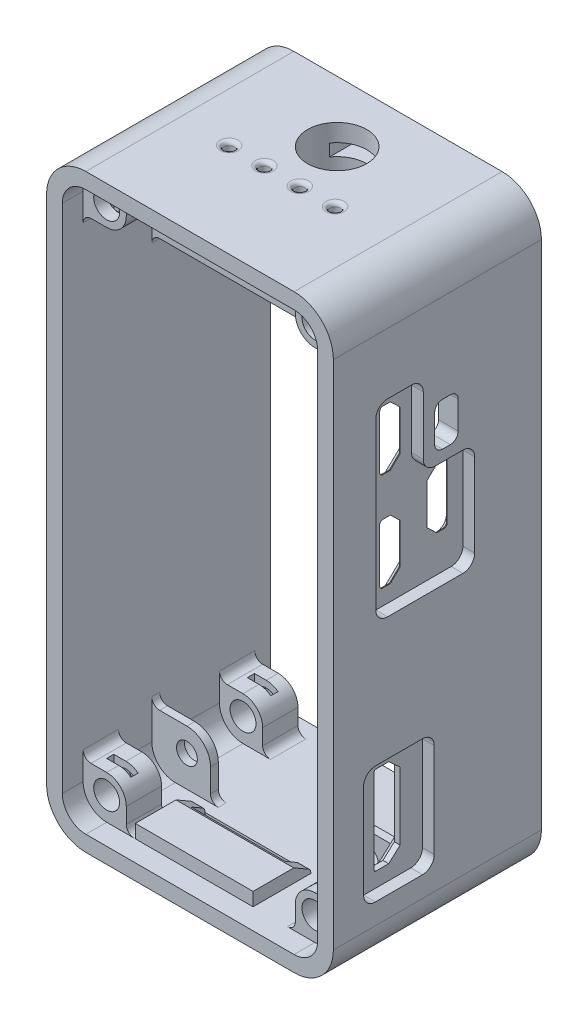
SolidWorks part; units mm, degrees
ref_plane "Front Plane" through (0, 0, 0) normal (0, 0, 1) x (1, 0, 0)
ref_plane "Top Plane" through (0, 0, 0) normal (0, 1, 0) x (1, 0, 0)
ref_plane "Right Plane" through (0, 0, 0) normal (1, 0, 0) x (0, 0, -1)
ref_plane "Plane1" through (15.42, 0, 0) normal (1, 0, 0) x (0, 0, -1)
ref_plane "Plane2" through (-16, 0, 0) normal (-1, 0, 0) x (0, 0, 1)
ref_plane "Plane3" through (0, 0, 12.35) normal (0, 0, -1) x (-1, 0, 0)
ref_plane "Plane4" through (0, 38.12, 0) normal (0, 1, 0) x (1, 0, 0)
ref_plane "Plane5" through (0, 0, -19.1) normal (0, 0, -1) x (-1, 0, 0)
ref_plane "Plane6" through (16.53, 0, 0) normal (1, 0, 0) x (0, 0, -1)
ref_plane "Plane7" through (0, -35, 0) normal (0, -1, 0) x (-1, 0, 0)
ref_axis "Axis1" through (16.53, -35, -39.8418) along (0, 0, 1)
ref_axis "Axis2" through (16.53, 38.12, 31.0702) along (0, 0, -1)
ref_axis "Axis3" through (16.53, 41.9436, 12.35) along (0, -1, 0)
ref_axis "Axis4" through (16.53, 40.8595, -19.1) along (0, -1, 0)
sketch "Sketch1" plane through (16.53, 0, 0) normal (1, 0, 0) x (0, 0, -1)
  line L0 (-31.0702, 38.12) -> (38.474, 38.12) construction
  line L1 (-12.35, 38.12) -> (19.1, 38.12)
  line L2 (-12.35, 38.12) -> (-12.35, -35)
  line L3 (-12.35, -35) -> (19.1, -35)
  line L4 (19.1, 38.12) -> (19.1, -35)
  line L6 (19.1, 40.8595) -> (19.1, -42.4423) construction
  line L7 (39.8418, -35) -> (-39.6201, -35) construction
  line L8 (-12.35, 41.9436) -> (-12.35, -39.5671) construction
extrude "Boss-Extrude1" add sketch "Sketch1" along normal blind 2
sketch "Sketch3" plane through (-16, 0, 0) normal (-1, 0, 0) x (0, 0, 1)
  line L4 (12.35, -35) -> (12.35, 38.12)
  line L5 (12.35, 38.12) -> (-19.1, 38.12)
  line L6 (-19.1, 38.12) -> (-19.1, -35)
  line L7 (-19.1, -35) -> (12.35, -35)
  line L8 (12.35, -35) -> (12.35, 38.12)
  line L9 (12.35, 38.12) -> (-19.1, 38.12)
  line L10 (-19.1, 38.12) -> (-19.1, -35)
  line L11 (-19.1, -35) -> (12.35, -35)
  dimension "D1" = 0
extrude "Boss-Extrude2" add sketch "Sketch3" along normal blind 2 separate body
sketch "Sketch4" plane through (0, 38.12, 0) normal (0, 1, 0) x (1, 0, 0)
  line L1 (-18, -12.35) -> (18.53, -12.35)
  line L2 (-18, -12.35) -> (-18, 19.1)
  line L3 (-18, 19.1) -> (18.53, 19.1)
  line L4 (18.53, -12.35) -> (18.53, 19.1)
extrude "Boss-Extrude3" add sketch "Sketch4" along normal blind 2
sketch "Sketch5" plane through (0, -35, 0) normal (0, -1, 0) x (1, 0, 0)
  line L1 (-18, 12.35) -> (18.53, 12.35)
  line L2 (-18, 12.35) -> (-18, -19.1)
  line L3 (-18, -19.1) -> (18.53, -19.1)
  line L4 (18.53, 12.35) -> (18.53, -19.1)
extrude "Boss-Extrude4" add sketch "Sketch5" against normal blind 2
fillet "Fillet1" radius 3 4 edges at (16.53, -33, -3.375) (16.53, 38.12, -3.375) (-16, 38.12, -3.375) (-16, -33, -3.375)
fillet "Fillet2" radius 5 4 edges at (-18, -35, -3.375) (18.53, -35, -3.375) (-18, 40.12, -3.375) (18.53, 40.12, -3.375)
sketch "Sketch6" plane through (18.53, 0, 0) normal (1, 0, 0) x (0, 0, -1)
  line L0 (-3.0523, 25.35) -> (-3.6, 25.35) construction
  line L3 (-2.3598, 18.0786) -> (-1.7075, 18.7048) construction
  line L4 (-3.6, 17.8) -> (-3.0523, 17.8) construction
  line L5 (-4, 24.95) -> (-4, 18.2) construction
  line L6 (-4, 24.95) -> (-4, 18.2)
  line L7 (-3.6, 17.8) -> (-2.65, 17.8)
  line L8 (-2.65, 17.8) -> (-1.4, 19)
  line L11 (-2.65, 25.35) -> (-3.6, 25.35)
  line L12 (-3.6, 5.3) -> (-3.0523, 5.3) construction
  line L13 (-2.3598, 5.5786) -> (-1.7075, 6.2048) construction
  line L14 (-1.4, 6.9262) -> (-1.4, 11.2238) construction
  line L15 (-1.7075, 11.9452) -> (-2.3598, 12.5714) construction
  line L16 (-3.0523, 12.85) -> (-3.6, 12.85) construction
  line L17 (-4, 12.45) -> (-4, 5.7) construction
  line L18 (-3.6, 5.3) -> (-2.65, 5.3)
  line L19 (-2.65, 5.3) -> (-1.4, 6.5)
  line L20 (-1.4, 6.5) -> (-1.4, 11.65)
  line L21 (-1.4, 11.65) -> (-2.65, 12.85)
  line L22 (-2.65, 12.85) -> (-3.6, 12.85)
  line L23 (-4, 12.45) -> (-4, 5.7)
  line L24 (4.2, 15.5) -> (3.6523, 15.5) construction
  line L25 (4.6, 8.35) -> (4.6, 15.1) construction
  line L26 (3.6523, 7.95) -> (4.2, 7.95) construction
  line L27 (2.3075, 8.8548) -> (2.9598, 8.2286) construction
  line L28 (2, 23.3) -> (2, 18.8)
  line L29 (2, 18.8) -> (4, 18.8)
  line L30 (4, 18.8) -> (4, 23.3)
  line L31 (4, 23.3) -> (2, 23.3)
  line L32 (2, 23.3) -> (2, 18.8) construction
  line L33 (2, 18.8) -> (4, 18.8) construction
  line L34 (4, 18.8) -> (4, 23.3) construction
  line L35 (4, 23.3) -> (2, 23.3) construction
  line L36 (2.5, 20.1) -> (3.5, 20.1)
  line L37 (3.5, 20.1) -> (3.5, 22)
  line L38 (3.5, 22) -> (2.5, 22)
  line L39 (2.5, 22) -> (2.5, 20.1)
  line L40 (2.5, 20.1) -> (3.5, 20.1) construction
  line L41 (3.5, 20.1) -> (3.5, 22) construction
  line L42 (3.5, 22) -> (2.5, 22) construction
  line L43 (2.5, 22) -> (2.5, 20.1) construction
  line L44 (2, 13.8738) -> (2, 9.5762) construction
  line L45 (2.9598, 15.2214) -> (2.3075, 14.5952) construction
  line L46 (4.2, 15.5) -> (3.25, 15.5)
  line L47 (4.6, 8.35) -> (4.6, 15.1)
  line L48 (3.25, 7.95) -> (4.2, 7.95)
  line L49 (2, 9.15) -> (3.25, 7.95)
  line L50 (2, 14.3) -> (2, 9.15)
  line L51 (3.25, 15.5) -> (2, 14.3)
  line L52 (-4.7, -14.45) -> (-4.7, -25.3) construction
  line L53 (-4.5, -25.5) -> (-2.9276, -25.5) construction
  line L54 (-2.7927, -25.4476) -> (-1.4651, -24.2345) construction
  line L55 (-2.9276, -14.25) -> (-4.5, -14.25) construction
  line L56 (-1.4651, -15.5155) -> (-2.7927, -14.3024) construction
  line L57 (-1.4, -24.0868) -> (-1.4, -15.6632) construction
  line L58 (-2.85, -14.25) -> (-4.5, -14.25)
  line L59 (-1.4, -15.575) -> (-2.85, -14.25)
  line L60 (-1.4, -24.175) -> (-1.4, -15.575)
  line L61 (-2.85, -25.5) -> (-1.4, -24.175)
  line L62 (-4.5, -25.5) -> (-2.85, -25.5)
  line L63 (-4.7, -14.45) -> (-4.7, -25.3)
  line L64 (-1.4, 24.15) -> (-2.65, 25.35)
  line L65 (-1.4, 19) -> (-1.4, 24.15)
  line L66 (1.5, 22.8) -> (1.5, 19.3)
  line L67 (2.5, 18.3) -> (3.5, 18.3)
  line L68 (4.5, 19.3) -> (4.5, 22.8)
  line L69 (3.5, 23.8) -> (2.5, 23.8)
  line L70 (1.5, 23.8) -> (1.5, 18.3) construction
  line L71 (1.5, 18.3) -> (4.5, 18.3) construction
  line L72 (4.5, 18.3) -> (4.5, 23.8) construction
  line L73 (4.5, 23.8) -> (1.5, 23.8) construction
  arc A0 (-4, 18.2) -> (-3.6, 17.8) centre (-3.6, 18.2) ccw construction
  arc A1 (-3.6, 25.35) -> (-4, 24.95) centre (-3.6, 24.95) ccw construction
  arc A6 (-4, 18.2) -> (-3.6, 17.8) centre (-3.6, 18.2) ccw
  arc A11 (-3.6, 25.35) -> (-4, 24.95) centre (-3.6, 24.95) ccw
  arc A12 (-4, 5.7) -> (-3.6, 5.3) centre (-3.6, 5.7) ccw construction
  arc A17 (-3.6, 12.85) -> (-4, 12.45) centre (-3.6, 12.45) ccw construction
  arc A18 (-4, 5.7) -> (-3.6, 5.3) centre (-3.6, 5.7) ccw
  arc A23 (-3.6, 12.85) -> (-4, 12.45) centre (-3.6, 12.45) ccw
  arc A25 (4.6, 15.1) -> (4.2, 15.5) centre (4.2, 15.1) ccw construction
  arc A26 (4.2, 7.95) -> (4.6, 8.35) centre (4.2, 8.35) ccw construction
  arc A31 (4.6, 15.1) -> (4.2, 15.5) centre (4.2, 15.1) ccw
  arc A32 (4.2, 7.95) -> (4.6, 8.35) centre (4.2, 8.35) ccw
  arc A37 (-4.7, -25.3) -> (-4.5, -25.5) centre (-4.5, -25.3) ccw construction
  arc A38 (-4.5, -14.25) -> (-4.7, -14.45) centre (-4.5, -14.45) ccw construction
  arc A42 (-4.5, -14.25) -> (-4.7, -14.45) centre (-4.5, -14.45) ccw
  arc A47 (-4.7, -25.3) -> (-4.5, -25.5) centre (-4.5, -25.3) ccw
  arc A48 (1.5, 19.3) -> (2.5, 18.3) centre (2.5, 19.3) ccw
  arc A49 (3.5, 18.3) -> (4.5, 19.3) centre (3.5, 19.3) ccw
  arc A50 (4.5, 22.8) -> (3.5, 23.8) centre (3.5, 22.8) ccw
  arc A51 (1.5, 22.8) -> (2.5, 23.8) centre (2.5, 22.8) cw
  dimension "D4" = 1
  dimension "D1" = 0
  dimension "D2" = 0
  dimension "D3" = 0.5
extrude "Cut-Extrude1" cut sketch "Sketch6" against normal blind 4
sketch "Sketch7" plane through (18.53, 0, 0) normal (1, 0, 0) x (0, 0, -1)
  line L0 (3.3166, 18.3) -> (3.3166, 15.5) construction
  line L1 (2.5, 18.3) -> (3.5, 18.3) construction
  line L2 (4.2, 15.5) -> (3.25, 15.5) construction
  line L3 (-1.4, 21.575) -> (1.5, 21.575) construction
  line L4 (-1.4, 19) -> (-1.4, 24.15) construction
  line L5 (1.5, 22.8) -> (1.5, 19.3) construction
  line L6 (0.05, 25.85) -> (0.05, 18.4)
  line L7 (1.55, 16.9) -> (5.1, 16.9)
  line L8 (-6, 25.85) -> (-6, 4.8)
  line L9 (-4, 24.95) -> (-4, 18.2) construction
  line L10 (-4.5, 27.35) -> (-1.45, 27.35)
  line L11 (-2.65, 25.35) -> (-3.6, 25.35) construction
  line L12 (-4.5, 3.3) -> (5.1, 3.3)
  line L13 (6.6, 4.8) -> (6.6, 15.4)
  line L14 (-3.6, 5.3) -> (-2.65, 5.3) construction
  line L15 (4.6, 8.35) -> (4.6, 15.1) construction
  line L16 (-4.7, -19.875) -> (-1.4, -19.875) construction
  line L17 (-6.05, -12.375) -> (-0.05, -12.375)
  line L18 (-7.55, -13.875) -> (-7.55, -25.875)
  line L19 (-6.05, -27.375) -> (-0.05, -27.375)
  line L20 (1.45, -13.875) -> (1.45, -25.875)
  line L21 (-4.7, -14.45) -> (-4.7, -25.3) construction
  line L22 (-1.4, -24.175) -> (-1.4, -15.575) construction
  line L23 (-3.05, -12.375) -> (-3.05, -27.375) construction
  arc A0 (-6, 4.8) -> (-4.5, 3.3) centre (-4.5, 4.8) ccw
  arc A1 (5.1, 3.3) -> (6.6, 4.8) centre (5.1, 4.8) ccw
  arc A2 (5.1, 16.9) -> (6.6, 15.4) centre (5.1, 15.4) cw
  arc A3 (1.55, 16.9) -> (0.05, 18.4) centre (1.55, 18.4) cw
  arc A4 (0.05, 25.85) -> (-1.45, 27.35) centre (-1.45, 25.85) ccw
  arc A5 (-6, 25.85) -> (-4.5, 27.35) centre (-4.5, 25.85) cw
  arc A6 (-0.05, -27.375) -> (1.45, -25.875) centre (-0.05, -25.875) ccw
  arc A7 (-0.05, -12.375) -> (1.45, -13.875) centre (-0.05, -13.875) cw
  arc A8 (-6.05, -12.375) -> (-7.55, -13.875) centre (-6.05, -13.875) ccw
  arc A9 (-7.55, -25.875) -> (-6.05, -27.375) centre (-6.05, -25.875) ccw
  point P14 (0.05, 21.575)
  point P17 (3.3166, 16.9)
  point P50 (-7.55, -19.875)
  point P53 (-3.05, -19.875)
  point P54 (-3.05, -19.875)
  dimension "D5" = 1.5
  dimension "D8" = 1.5
  dimension "D1" = 2
  dimension "D2" = 2
  dimension "D3" = 2
  dimension "D4" = 2
  dimension "D6" = 9
  dimension "D7" = 15
extrude "Cut-Extrude2" cut sketch "Sketch7" against normal blind 1.5
sketch "Sketch8" plane through (16.53, 0, 0) normal (-1, 0, 0) x (0, 0, 1)
  line L0 (7.2, 4.8) -> (7.2, 25.85)
  line L1 (4.5, 28.55) -> (1.45, 28.55)
  line L4 (-7.8, 15.4) -> (-7.8, 25.85)
  line L5 (-5.1, 28.55) -> (1.45, 28.55)
  line L6 (-5.1, 3.3) -> (4.5, 3.3)
  line L7 (-6.6, 15.4) -> (-6.6, 4.8)
  line L8 (-1.55, 16.9) -> (-5.1, 16.9)
  line L9 (-0.05, 25.85) -> (-0.05, 18.4)
  line L10 (4.5, 27.35) -> (1.45, 27.35)
  line L11 (6, 4.8) -> (6, 25.85)
  line L12 (-5.1, 3.3) -> (4.5, 3.3) construction
  line L13 (-6.6, 15.4) -> (-6.6, 4.8) construction
  line L14 (-1.55, 16.9) -> (-5.1, 16.9) construction
  line L15 (-0.05, 25.85) -> (-0.05, 18.4) construction
  line L16 (4.5, 27.35) -> (1.45, 27.35) construction
  line L17 (6, 4.8) -> (6, 25.85) construction
  line L18 (-2.5, 18.3) -> (-3.5, 18.3) construction
  line L19 (-1.5, 22.8) -> (-1.5, 19.3) construction
  line L24 (-7.8, 15.4) -> (-7.8, 4.8)
  line L25 (-5.1, 2.1) -> (4.5, 2.1)
  line L42 (2.65, 25.35) -> (1.4, 24.15) construction
  line L43 (3.6, 25.35) -> (2.65, 25.35) construction
  line L44 (4, 18.2) -> (4, 24.95) construction
  line L45 (2.65, 17.8) -> (3.6, 17.8) construction
  line L46 (1.4, 19) -> (2.65, 17.8) construction
  line L47 (1.4, 24.15) -> (1.4, 19) construction
  line L48 (2.65, 25.35) -> (1.4, 24.15)
  line L49 (3.6, 25.35) -> (2.65, 25.35)
  line L50 (4, 18.2) -> (4, 24.95)
  line L51 (2.65, 17.8) -> (3.6, 17.8)
  line L52 (1.4, 19) -> (2.65, 17.8)
  line L53 (1.4, 24.15) -> (1.4, 19)
  line L54 (1.4, 11.65) -> (1.4, 6.5) construction
  line L55 (1.4, 6.5) -> (2.65, 5.3) construction
  line L56 (2.65, 5.3) -> (3.6, 5.3) construction
  line L57 (4, 5.7) -> (4, 12.45) construction
  line L58 (2.65, 12.85) -> (1.4, 11.65) construction
  line L59 (3.6, 12.85) -> (2.65, 12.85) construction
  line L60 (1.4, 11.65) -> (1.4, 6.5)
  line L61 (1.4, 6.5) -> (2.65, 5.3)
  line L62 (2.65, 5.3) -> (3.6, 5.3)
  line L63 (4, 5.7) -> (4, 12.45)
  line L64 (2.65, 12.85) -> (1.4, 11.65)
  line L65 (3.6, 12.85) -> (2.65, 12.85)
  line L66 (-4.2, 7.95) -> (-3.25, 7.95) construction
  line L67 (-4.6, 15.1) -> (-4.6, 8.35) construction
  line L68 (-3.25, 15.5) -> (-4.2, 15.5) construction
  line L69 (-2, 14.3) -> (-3.25, 15.5) construction
  line L70 (-2, 9.15) -> (-2, 14.3) construction
  line L71 (-3.25, 7.95) -> (-2, 9.15) construction
  line L72 (-4.2, 7.95) -> (-3.25, 7.95)
  line L73 (-4.6, 15.1) -> (-4.6, 8.35)
  line L74 (-3.25, 15.5) -> (-4.2, 15.5)
  line L75 (-2, 14.3) -> (-3.25, 15.5)
  line L76 (-2, 9.15) -> (-2, 14.3)
  line L77 (-3.25, 7.95) -> (-2, 9.15)
  line L78 (-3.5, 23.8) -> (-2.5, 23.8) construction
  line L79 (-4.5, 19.3) -> (-4.5, 22.8) construction
  line L80 (-2.5, 18.3) -> (-3.5, 18.3)
  line L81 (-1.5, 22.8) -> (-1.5, 19.3)
  line L82 (-3.5, 23.8) -> (-2.5, 23.8)
  line L83 (-4.5, 19.3) -> (-4.5, 22.8)
  line L88 (-1.25, 25.85) -> (-1.25, 18.4) construction
  line L89 (-1.55, 18.1) -> (-5.1, 18.1) construction
  arc A0 (4.5, 2.1) -> (7.2, 4.8) centre (4.5, 4.8) ccw
  arc A1 (7.2, 25.85) -> (4.5, 28.55) centre (4.5, 25.85) ccw
  arc A4 (-7.8, 25.85) -> (-5.1, 28.55) centre (-5.1, 25.85) cw
  arc A5 (-4.5, 19.3) -> (-3.5, 18.3) centre (-3.5, 19.3) ccw construction
  arc A6 (4.5, 3.3) -> (6, 4.8) centre (4.5, 4.8) ccw
  arc A7 (-6.6, 4.8) -> (-5.1, 3.3) centre (-5.1, 4.8) ccw
  arc A8 (-5.1, 16.9) -> (-6.6, 15.4) centre (-5.1, 15.4) ccw
  arc A9 (-1.55, 16.9) -> (-0.05, 18.4) centre (-1.55, 18.4) ccw
  arc A10 (1.45, 27.35) -> (-0.05, 25.85) centre (1.45, 25.85) ccw
  arc A11 (6, 25.85) -> (4.5, 27.35) centre (4.5, 25.85) ccw
  arc A12 (4.5, 3.3) -> (6, 4.8) centre (4.5, 4.8) ccw construction
  arc A13 (-6.6, 4.8) -> (-5.1, 3.3) centre (-5.1, 4.8) ccw construction
  arc A14 (-5.1, 16.9) -> (-6.6, 15.4) centre (-5.1, 15.4) ccw construction
  arc A15 (-1.55, 16.9) -> (-0.05, 18.4) centre (-1.55, 18.4) ccw construction
  arc A16 (1.45, 27.35) -> (-0.05, 25.85) centre (1.45, 25.85) ccw construction
  arc A17 (6, 25.85) -> (4.5, 27.35) centre (4.5, 25.85) ccw construction
  arc A18 (-2.5, 18.3) -> (-1.5, 19.3) centre (-2.5, 19.3) ccw construction
  arc A19 (-1.5, 22.8) -> (-2.5, 23.8) centre (-2.5, 22.8) ccw construction
  arc A25 (-7.8, 4.8) -> (-5.1, 2.1) centre (-5.1, 4.8) ccw
  arc A34 (4, 24.95) -> (3.6, 25.35) centre (3.6, 24.95) ccw construction
  arc A35 (3.6, 17.8) -> (4, 18.2) centre (3.6, 18.2) ccw construction
  arc A36 (4, 24.95) -> (3.6, 25.35) centre (3.6, 24.95) ccw
  arc A37 (3.6, 17.8) -> (4, 18.2) centre (3.6, 18.2) ccw
  arc A38 (3.6, 5.3) -> (4, 5.7) centre (3.6, 5.7) ccw construction
  arc A39 (4, 12.45) -> (3.6, 12.85) centre (3.6, 12.45) ccw construction
  arc A40 (3.6, 5.3) -> (4, 5.7) centre (3.6, 5.7) ccw
  arc A41 (4, 12.45) -> (3.6, 12.85) centre (3.6, 12.45) ccw
  arc A42 (-4.6, 8.35) -> (-4.2, 7.95) centre (-4.2, 8.35) ccw construction
  arc A43 (-4.2, 15.5) -> (-4.6, 15.1) centre (-4.2, 15.1) ccw construction
  arc A44 (-4.6, 8.35) -> (-4.2, 7.95) centre (-4.2, 8.35) ccw
  arc A45 (-4.2, 15.5) -> (-4.6, 15.1) centre (-4.2, 15.1) ccw
  arc A46 (-3.5, 23.8) -> (-4.5, 22.8) centre (-3.5, 22.8) ccw construction
  arc A47 (-4.5, 19.3) -> (-3.5, 18.3) centre (-3.5, 19.3) ccw
  arc A48 (-2.5, 18.3) -> (-1.5, 19.3) centre (-2.5, 19.3) ccw
  arc A49 (-1.5, 22.8) -> (-2.5, 23.8) centre (-2.5, 22.8) ccw
  arc A50 (-3.5, 23.8) -> (-4.5, 22.8) centre (-3.5, 22.8) ccw
  arc A56 (1.45, 28.55) -> (-1.25, 25.85) centre (1.45, 25.85) ccw construction
  arc A57 (-1.55, 18.1) -> (-1.25, 18.4) centre (-1.55, 18.4) ccw construction
  arc A58 (-5.1, 18.1) -> (-7.8, 15.4) centre (-5.1, 15.4) ccw construction
  dimension "D2" = 2.7
  dimension "D1" = 0
  dimension "D3" = 1.2
extrude "Boss-Extrude5" add sketch "Sketch8" along normal blind 0.5
sketch "Sketch9" plane through (16.53, 0, 0) normal (-1, 0, 0) x (0, 0, 1)
  line L0 (0.05, -28.575) -> (6.05, -28.575)
  line L1 (8.75, -25.875) -> (8.75, -13.875)
  line L2 (6.05, -11.175) -> (0.05, -11.175)
  line L3 (-2.65, -13.875) -> (-2.65, -25.875)
  line L4 (-1.45, -13.875) -> (-1.45, -25.875)
  line L5 (6.05, -12.375) -> (0.05, -12.375)
  line L6 (7.55, -25.875) -> (7.55, -13.875)
  line L7 (0.05, -27.375) -> (6.05, -27.375)
  line L8 (-1.45, -13.875) -> (-1.45, -25.875) construction
  line L9 (6.05, -12.375) -> (0.05, -12.375) construction
  line L10 (7.55, -25.875) -> (7.55, -13.875) construction
  line L11 (0.05, -27.375) -> (6.05, -27.375) construction
  line L12 (1.4, -24.175) -> (2.85, -25.5) construction
  line L13 (2.85, -25.5) -> (4.5, -25.5) construction
  line L14 (1.4, -15.575) -> (1.4, -24.175) construction
  line L15 (2.85, -14.25) -> (1.4, -15.575) construction
  line L16 (4.5, -14.25) -> (2.85, -14.25) construction
  line L17 (4.7, -25.3) -> (4.7, -14.45) construction
  line L18 (1.4, -24.175) -> (2.85, -25.5)
  line L19 (2.85, -25.5) -> (4.5, -25.5)
  line L20 (1.4, -15.575) -> (1.4, -24.175)
  line L21 (2.85, -14.25) -> (1.4, -15.575)
  line L22 (4.5, -14.25) -> (2.85, -14.25)
  line L23 (4.7, -25.3) -> (4.7, -14.45)
  line L24 (8.75, -25.875) -> (8.75, -28.575)
  line L25 (8.75, -28.575) -> (6.05, -28.575)
  arc A0 (-2.65, -25.875) -> (0.05, -28.575) centre (0.05, -25.875) ccw
  arc A1 (6.05, -28.575) -> (8.75, -25.875) centre (6.05, -25.875) ccw construction
  arc A2 (8.75, -13.875) -> (6.05, -11.175) centre (6.05, -13.875) ccw
  arc A3 (0.05, -11.175) -> (-2.65, -13.875) centre (0.05, -13.875) ccw
  arc A4 (-1.45, -25.875) -> (0.05, -27.375) centre (0.05, -25.875) ccw
  arc A5 (0.05, -12.375) -> (-1.45, -13.875) centre (0.05, -13.875) ccw
  arc A6 (7.55, -13.875) -> (6.05, -12.375) centre (6.05, -13.875) ccw
  arc A7 (6.05, -27.375) -> (7.55, -25.875) centre (6.05, -25.875) ccw
  arc A8 (-1.45, -25.875) -> (0.05, -27.375) centre (0.05, -25.875) ccw construction
  arc A9 (0.05, -12.375) -> (-1.45, -13.875) centre (0.05, -13.875) ccw construction
  arc A10 (7.55, -13.875) -> (6.05, -12.375) centre (6.05, -13.875) ccw construction
  arc A11 (6.05, -27.375) -> (7.55, -25.875) centre (6.05, -25.875) ccw construction
  arc A12 (4.5, -25.5) -> (4.7, -25.3) centre (4.5, -25.3) ccw construction
  arc A13 (4.7, -14.45) -> (4.5, -14.25) centre (4.5, -14.45) ccw construction
  arc A14 (4.5, -25.5) -> (4.7, -25.3) centre (4.5, -25.3) ccw
  arc A15 (4.7, -14.45) -> (4.5, -14.25) centre (4.5, -14.45) ccw
  dimension "D1" = 0
  dimension "D2" = 1.2
extrude "Boss-Extrude6" add sketch "Sketch9" along normal up to surface (1.13 mm away)
chamfer "Chamfer1" distance 0.9 angle 45 32 edges at (16.03, 12.25, 2.025) (16.03, 5.9, 2.025) (16.03, 9.075, 1.4) (16.03, 24.75, 2.025) (16.03, 18.4, 2.025) (16.03, 21.575, 1.4) (16.03, 8.55, -2.625) (16.03, 14.9, -2.625) (16.03, 11.725, -2) (16.03, 15.5, -3.725) (16.03, 7.95, -3.725) (16.03, 15.3828, -4.4828) (16.03, 8.0672, -4.4828) (16.03, 11.725, -4.6) (16.03, 5.3, 3.125) (16.03, 12.85, 3.125) (16.03, 5.4172, 3.8828) (16.03, 12.7328, 3.8828) (16.03, 9.075, 4) (16.03, 17.8, 3.125) (16.03, 25.35, 3.125) (16.03, 17.9172, 3.8828) (16.03, 25.2328, 3.8828) (16.03, 21.575, 4) (15.4, -14.9125, 2.125) (15.4, -19.875, 1.4) (15.4, -24.8375, 2.125) (15.4, -25.5, 3.675) (15.4, -14.25, 3.675) (15.4, -25.4414, 4.6414) (15.4, -14.3086, 4.6414) (15.4, -19.875, 4.7)
sketch "Sketch10" plane through (0, -35, 0) normal (0, -1, 0) x (1, 0, 0)
  line L0 (4.15, 2.75) -> (4.15, 1.4) construction
  line L1 (1.65, 2.85) -> (4.05, 2.85) construction
  line L2 (4.15, 1.4) -> (1.65, 1.4) construction
  line L3 (1.65, 1.4) -> (1.65, 2.85) construction
  line L4 (-7.85, 1.4) -> (-7.85, 2.75) construction
  line L5 (-7.75, 2.85) -> (-6.75, 2.85) construction
  line L6 (-6.75, 2.85) -> (-6.75, 1.4) construction
  line L7 (-6.75, 1.4) -> (-7.85, 1.4) construction
  line L8 (1.65, 2.85) -> (4.05, 2.85) construction
  line L9 (4.15, 2.75) -> (4.15, 1.4) construction
  line L10 (4.15, 1.4) -> (1.65, 1.4) construction
  line L11 (1.65, 1.4) -> (1.65, 2.85) construction
  line L12 (-7.85, 1.4) -> (-7.85, 2.75) construction
  line L13 (-7.75, 2.85) -> (-6.75, 2.85) construction
  line L14 (-6.75, 2.85) -> (-6.75, 1.4) construction
  line L15 (-6.75, 1.4) -> (-7.85, 1.4) construction
  line L17 (4.15, 1.4) -> (-7.85, 1.4)
  line L18 (4.15, 1.4) -> (4.15, 3.1408)
  line L19 (4.15, 3.1408) -> (-7.85, 3.1408)
  line L20 (-7.85, 1.4) -> (-7.85, 3.1408)
  arc A0 (4.15, 2.75) -> (4.05, 2.85) centre (4.05, 2.75) ccw construction
  arc A1 (-7.75, 2.85) -> (-7.85, 2.75) centre (-7.75, 2.75) ccw construction
  arc A2 (4.15, 2.75) -> (4.05, 2.85) centre (4.05, 2.75) ccw construction
  arc A3 (-7.75, 2.85) -> (-7.85, 2.75) centre (-7.75, 2.75) ccw construction
extrude "Cut-Extrude3" cut sketch "Sketch10" against normal blind 3
sketch "Sketch11" plane through (0, -33, 0) normal (0, 1, 0) x (1, 0, 0)
  line L0 (-7.85, -1.4) -> (4.15, -1.4) construction
  line L1 (5.65, -7.1408) -> (-9.35, -7.1408)
  line L2 (5.65, -7.1408) -> (5.65, -1.4)
  line L3 (5.65, -1.4) -> (4.15, -1.4)
  line L4 (-9.35, -7.1408) -> (-9.35, -1.4)
  line L5 (4.15, -1.4) -> (4.15, -3.1408) construction
  line L6 (-7.85, -3.1408) -> (-7.85, -1.4) construction
  line L7 (4.15, -3.1408) -> (-7.85, -3.1408) construction
  line L8 (4.15, -1.4) -> (4.15, -3.1408) construction
  line L9 (4.15, -3.1408) -> (-7.85, -3.1408) construction
  line L10 (-7.85, -3.1408) -> (-7.85, -1.4) construction
  line L11 (4.15, -1.4) -> (4.15, -3.1408)
  line L12 (4.15, -3.1408) -> (-7.85, -3.1408)
  line L13 (-7.85, -3.1408) -> (-7.85, -1.4)
  line L14 (-7.85, -1.4) -> (-9.35, -1.4)
  dimension "D1" = 1.5
  dimension "D2" = 1.5
  dimension "D3" = 4
extrude "Boss-Extrude7" add sketch "Sketch11" along normal blind 1.7
sketch "Sketch12" plane through (0, 0, 3.1408) normal (0, 0, -1) x (-1, 0, 0)
  line L0 (-4.15, -35) -> (7.85, -35) construction
  line L1 (-4.15, -35) -> (7.85, -35) construction
  line L2 (9.4089, -39.5975) -> (-5.7089, -39.5975)
  arc A0 (9.4089, -39.5975) -> (-5.7089, -39.5975) centre (1.85, -39.5975) ccw
revolve "Cut-Revolve1" cut sketch "Sketch12" angle 90 about L2
fillet "Fillet4" radius 0.5 1 edges at (-1.85, -32.0386, 3.1408)
sketch "Sketch14" plane through (0, 40.12, 0) normal (0, 1, 0) x (1, 0, 0)
  line L0 (7.4, 1) -> (6.1, 1) construction
  line L1 (6.1, 1) -> (6.1, 0.8) construction
  line L2 (6.1, 0.8) -> (7.4, 0.8) construction
  line L3 (7.4, 0.8) -> (7.4, 1) construction
  line L4 (7.4, 0.8) -> (6.1, 0.8) construction
  line L5 (6.1, 0.8) -> (6.1, 0.2) construction
  line L6 (6.1, 0.2) -> (7.4, 0.2) construction
  line L7 (7.4, 0.2) -> (7.4, 0.8) construction
  line L8 (7.4, 1) -> (6.1, 1) construction
  line L9 (6.1, 1) -> (6.1, 0.8) construction
  line L10 (6.1, 0.8) -> (7.4, 0.8) construction
  line L11 (7.4, 0.8) -> (7.4, 1) construction
  line L12 (7.4, 0.8) -> (6.1, 0.8) construction
  line L13 (6.1, 0.8) -> (6.1, 0.2) construction
  line L14 (6.1, 0.2) -> (7.4, 0.2) construction
  line L15 (7.4, 0.2) -> (7.4, 0.8) construction
  line L16 (2.9, 1) -> (1.6, 1) construction
  line L17 (1.6, 1) -> (1.6, 0.8) construction
  line L18 (1.6, 0.8) -> (2.9, 0.8) construction
  line L19 (2.9, 0.8) -> (2.9, 1) construction
  line L20 (2.9, 0.8) -> (1.6, 0.8) construction
  line L21 (1.6, 0.8) -> (1.6, 0.2) construction
  line L22 (1.6, 0.2) -> (2.9, 0.2) construction
  line L23 (2.9, 0.2) -> (2.9, 0.8) construction
  line L24 (2.9, 1) -> (1.6, 1) construction
  line L25 (1.6, 1) -> (1.6, 0.8) construction
  line L26 (1.6, 0.8) -> (2.9, 0.8) construction
  line L27 (2.9, 0.8) -> (2.9, 1) construction
  line L28 (2.9, 0.8) -> (1.6, 0.8) construction
  line L29 (1.6, 0.8) -> (1.6, 0.2) construction
  line L30 (1.6, 0.2) -> (2.9, 0.2) construction
  line L31 (2.9, 0.2) -> (2.9, 0.8) construction
  line L32 (-1.6, 1) -> (-2.9, 1) construction
  line L33 (-2.9, 1) -> (-2.9, 0.8) construction
  line L34 (-2.9, 0.8) -> (-1.6, 0.8) construction
  line L35 (-1.6, 0.8) -> (-1.6, 1) construction
  line L36 (-1.6, 0.8) -> (-2.9, 0.8) construction
  line L37 (-2.9, 0.8) -> (-2.9, 0.2) construction
  line L38 (-2.9, 0.2) -> (-1.6, 0.2) construction
  line L39 (-1.6, 0.2) -> (-1.6, 0.8) construction
  line L40 (-1.6, 1) -> (-2.9, 1) construction
  line L41 (-2.9, 1) -> (-2.9, 0.8) construction
  line L42 (-2.9, 0.8) -> (-1.6, 0.8) construction
  line L43 (-1.6, 0.8) -> (-1.6, 1) construction
  line L44 (-1.6, 0.8) -> (-2.9, 0.8) construction
  line L45 (-2.9, 0.8) -> (-2.9, 0.2) construction
  line L46 (-2.9, 0.2) -> (-1.6, 0.2) construction
  line L47 (-1.6, 0.2) -> (-1.6, 0.8) construction
  line L48 (-6.1, 1) -> (-7.4, 1) construction
  line L49 (-7.4, 1) -> (-7.4, 0.8) construction
  line L50 (-7.4, 0.8) -> (-6.1, 0.8) construction
  line L51 (-6.1, 0.8) -> (-6.1, 1) construction
  line L52 (-6.1, 0.8) -> (-7.4, 0.8) construction
  line L53 (-7.4, 0.8) -> (-7.4, 0.2) construction
  line L54 (-7.4, 0.2) -> (-6.1, 0.2) construction
  line L55 (-6.1, 0.2) -> (-6.1, 0.8) construction
  line L56 (-6.1, 1) -> (-7.4, 1) construction
  line L57 (-7.4, 1) -> (-7.4, 0.8) construction
  line L58 (-7.4, 0.8) -> (-6.1, 0.8) construction
  line L59 (-6.1, 0.8) -> (-6.1, 1) construction
  line L60 (-6.1, 0.8) -> (-7.4, 0.8) construction
  line L61 (-7.4, 0.8) -> (-7.4, 0.2) construction
  line L62 (-7.4, 0.2) -> (-6.1, 0.2) construction
  line L63 (-6.1, 0.2) -> (-6.1, 0.8) construction
  line L64 (6.75, 1) -> (6.75, 0.2) construction
  line L65 (2.25, 1) -> (2.25, 0.2) construction
  line L66 (-2.25, 1) -> (-2.25, 0.2) construction
  line L67 (-6.75, 1) -> (-6.75, 0.2) construction
  circle A0 centre (6.75, 0.6) radius 0.65
  circle A1 centre (2.25, 0.6) radius 0.65
  circle A2 centre (-2.25, 0.6) radius 0.65
  circle A3 centre (-6.75, 0.6) radius 0.65
  point P48 (6.75, -0.05)
extrude "Cut-Extrude4" cut sketch "Sketch14" against normal up to next
fillet "Fillet5" radius 0.5 4 edges at (-6.75, 40.12, 0.05) (-2.25, 40.12, 0.05) (2.25, 40.12, 0.05) (6.75, 40.12, 0.05)
sketch "Sketch15" plane through (0, 0, 0) normal (0, 0, -1) x (-1, 0, 0)
  line L0 (-13.53, 38.12) -> (13, 38.12) construction
  line L1 (16, 35.12) -> (16, -30) construction
  line L2 (-16.53, -30) -> (-16.53, 35.12) construction
  line L3 (13, -33) -> (-13.53, -33) construction
  line L4 (15, -28.75) -> (15, 28.75)
  line L5 (11.25, 32.5) -> (-11.25, 32.5)
  line L6 (-15, 28.75) -> (-15, -28.75)
  line L7 (-11.25, -32.5) -> (11.25, -32.5)
  line L8 (15, -28.75) -> (15, 28.75) construction
  line L9 (11.25, 32.5) -> (-11.25, 32.5) construction
  line L10 (-15, 28.75) -> (-15, -28.75) construction
  line L11 (-11.25, -32.5) -> (11.25, -32.5) construction
  line L12 (13, -33) -> (-13.53, -33)
  line L13 (-16.53, -30) -> (-16.53, 35.12)
  line L14 (16, 35.12) -> (16, -30)
  line L15 (-13.53, 38.12) -> (13, 38.12)
  circle A0 centre (11.525, 29.025) radius 1.325 construction
  circle A1 centre (11.525, 29.025) radius 1.325
  circle A2 centre (-11.525, 29.025) radius 1.325 construction
  circle A3 centre (-11.525, 29.025) radius 1.325
  arc A4 (11.25, -32.5) -> (15, -28.75) centre (11.25, -28.75) ccw
  arc A5 (15, 28.75) -> (11.25, 32.5) centre (11.25, 28.75) ccw
  arc A6 (-11.25, 32.5) -> (-15, 28.75) centre (-11.25, 28.75) ccw
  arc A7 (-15, -28.75) -> (-11.25, -32.5) centre (-11.25, -28.75) ccw
  arc A8 (11.25, -32.5) -> (15, -28.75) centre (11.25, -28.75) ccw construction
  arc A9 (15, 28.75) -> (11.25, 32.5) centre (11.25, 28.75) ccw construction
  arc A10 (-11.25, 32.5) -> (-15, 28.75) centre (-11.25, 28.75) ccw construction
  arc A11 (-15, -28.75) -> (-11.25, -32.5) centre (-11.25, -28.75) ccw construction
  circle A12 centre (-11.525, -29.025) radius 1.325 construction
  circle A13 centre (-11.525, -29.025) radius 1.325
  circle A14 centre (11.525, -29.025) radius 1.325 construction
  circle A15 centre (11.525, -29.025) radius 1.325
  arc A16 (-13.53, 38.12) -> (-16.53, 35.12) centre (-13.53, 35.12) ccw construction
  arc A17 (16, 35.12) -> (13, 38.12) centre (13, 35.12) ccw construction
  arc A18 (13, -33) -> (16, -30) centre (13, -30) ccw construction
  arc A19 (-16.53, -30) -> (-13.53, -33) centre (-13.53, -30) ccw construction
  arc A20 (13, -33) -> (16, -30) centre (13, -30) ccw
  arc A21 (-16.53, -30) -> (-13.53, -33) centre (-13.53, -30) ccw
  arc A22 (-13.53, 38.12) -> (-16.53, 35.12) centre (-13.53, 35.12) ccw
  arc A23 (16, 35.12) -> (13, 38.12) centre (13, 35.12) ccw
  dimension "D1" = 0
sketch "Sketch16" plane through (0, 0, 0) normal (0, 0, -1) x (-1, 0, 0)
  line L0 (-13.53, 38.12) -> (13, 38.12) construction
  line L1 (-16.53, -30) -> (-16.53, 35.12) construction
  line L2 (13, -33) -> (-13.53, -33) construction
  line L3 (16, 35.12) -> (16, -30) construction
  line L4 (-13.53, 38.12) -> (13, 38.12)
  line L5 (-16.53, -30) -> (-16.53, -26.025)
  line L6 (13, -33) -> (8.525, -33)
  line L7 (16, 35.12) -> (16, 26.025)
  line L8 (-8.525, -29.025) -> (-8.525, -33)
  line L9 (-11.525, -26.025) -> (-16.53, -26.025)
  line L10 (11.525, -26.025) -> (16, -26.025)
  line L11 (8.525, -29.025) -> (8.525, -33)
  line L12 (-16.53, 26.025) -> (16, 26.025)
  line L13 (-16.53, 26.025) -> (-16.53, 35.12)
  line L14 (16, -26.025) -> (16, -30)
  line L15 (-8.525, -33) -> (-13.53, -33)
  arc A0 (16, 35.12) -> (13, 38.12) centre (13, 35.12) ccw construction
  arc A1 (-13.53, 38.12) -> (-16.53, 35.12) centre (-13.53, 35.12) ccw construction
  arc A2 (-16.53, -30) -> (-13.53, -33) centre (-13.53, -30) ccw construction
  arc A3 (13, -33) -> (16, -30) centre (13, -30) ccw construction
  arc A4 (16, 35.12) -> (13, 38.12) centre (13, 35.12) ccw
  arc A5 (-13.53, 38.12) -> (-16.53, 35.12) centre (-13.53, 35.12) ccw
  arc A6 (-16.53, -30) -> (-13.53, -33) centre (-13.53, -30) ccw
  arc A7 (13, -33) -> (16, -30) centre (13, -30) ccw
  circle A8 centre (-11.525, 29.025) radius 1.325 construction
  circle A9 centre (-11.525, 29.025) radius 1.325
  circle A10 centre (11.525, 29.025) radius 1.325 construction
  circle A11 centre (11.525, 29.025) radius 1.325
  circle A12 centre (11.525, -29.025) radius 1.325 construction
  circle A13 centre (11.525, -29.025) radius 1.325
  circle A14 centre (-11.525, -29.025) radius 1.325 construction
  circle A15 centre (-11.525, -29.025) radius 1.325
  circle A16 centre (-11.525, -29.025) radius 3 construction
  circle A17 centre (11.525, -29.025) radius 3 construction
  circle A18 centre (-11.525, 29.025) radius 3 construction
  circle A19 centre (11.525, 29.025) radius 3 construction
  arc A20 (-8.525, -29.025) -> (-11.525, -26.025) centre (-11.525, -29.025) ccw
  arc A21 (11.525, -26.025) -> (8.525, -29.025) centre (11.525, -29.025) ccw
  circle A22 centre (-11.525, 29.025) radius 3 construction
  circle A23 centre (11.525, 29.025) radius 3 construction
extrude "Boss-Extrude8" add sketch "Sketch16" along normal blind 1
sketch "Sketch17" plane through (0, 0, 0) normal (0, 0, 1) x (1, 0, 0)
  line L0 (-11.25, 32.5) -> (11.25, 32.5) construction
  line L1 (-11.25, 32.5) -> (11.25, 32.5) construction
  line L2 (16.53, 32.7) -> (-16, 32.7)
  line L3 (16.53, -30) -> (16.53, 35.12) construction
  line L4 (-16, 35.12) -> (-16, -30) construction
  line L5 (13.53, 38.12) -> (-13, 38.12) construction
  line L6 (13.53, 38.12) -> (-13, 38.12)
  line L7 (-16, 35.12) -> (-16, 32.7)
  line L8 (16.53, 35.12) -> (16.53, 32.7)
  arc A0 (-13, 38.12) -> (-16, 35.12) centre (-13, 35.12) ccw construction
  arc A1 (16.53, 35.12) -> (13.53, 38.12) centre (13.53, 35.12) ccw construction
  arc A2 (-13, 38.12) -> (-16, 35.12) centre (-13, 35.12) ccw
  arc A3 (16.53, 35.12) -> (13.53, 38.12) centre (13.53, 35.12) ccw
  dimension "D1" = 0.2
extrude "Boss-Extrude9" add sketch "Sketch17" along normal blind 0.7
sketch "Sketch18" plane through (0, 0, -1) normal (0, 0, -1) x (-1, 0, 0)
  line L0 (7.4, 28.5) -> (6.1, 28.5) construction
  line L1 (2.9, 28.5) -> (1.6, 28.5) construction
  line L2 (-1.6, 28.5) -> (-2.9, 28.5) construction
  line L3 (-6.1, 28.5) -> (-7.4, 28.5) construction
  line L4 (7.4, 28.5) -> (6.1, 28.5)
  line L5 (2.9, 28.5) -> (1.6, 28.5)
  line L6 (-1.6, 28.5) -> (-2.9, 28.5)
  line L7 (-6.1, 28.5) -> (-7.4, 28.5)
  line L8 (-2.7623, 38.12) -> (-6.2377, 38.12) construction
  line L9 (-7.4, 28) -> (-6.1, 28)
  line L10 (-7.4, 28) -> (-7.4, 38.12)
  line L11 (-7.4, 38.12) -> (-6.1, 38.12)
  line L12 (-6.1, 28) -> (-6.1, 38.12)
  line L13 (1.7377, 38.12) -> (-1.7377, 38.12) construction
  line L14 (-2.9, 28) -> (-1.6, 28)
  line L15 (-2.9, 28) -> (-2.9, 38.12)
  line L16 (-2.9, 38.12) -> (-1.6, 38.12)
  line L17 (-1.6, 28) -> (-1.6, 38.12)
  line L18 (6.2377, 38.12) -> (2.7623, 38.12) construction
  line L19 (1.6, 28) -> (2.9, 28)
  line L20 (1.6, 28) -> (1.6, 38.12)
  line L21 (1.6, 38.12) -> (2.9, 38.12)
  line L22 (2.9, 28) -> (2.9, 38.12)
  line L23 (13, 38.12) -> (7.2623, 38.12) construction
  line L24 (6.1, 28) -> (7.4, 28)
  line L25 (6.1, 28) -> (6.1, 38.12)
  line L26 (6.1, 38.12) -> (7.4, 38.12)
  line L27 (7.4, 28) -> (7.4, 38.12)
  line L28 (-6.75, 28.5) -> (-6.75, 28) construction
  line L29 (-2.25, 28.5) -> (-2.25, 28) construction
  line L30 (2.25, 28.5) -> (2.25, 28) construction
  line L31 (6.75, 28.5) -> (6.75, 28) construction
  line L32 (-6.1, 38.12) -> (-7.4, 38.12) construction
  line L33 (-6.1, 38.12) -> (-7.4, 38.12)
  dimension "D1" = 0.5
extrude "Cut-Extrude5" cut sketch "Sketch18" against normal up to vertex (1.05 mm away) contours L9 L12 L10 | L14 L17 L15 | L19 L22 L20 | L24 L27 L25 region at (6.75, 33.31, -1) region at (2.25, 33.31, -1) region at (-2.25, 33.31, -1) region at (-6.75, 33.31, -1) up to point (6.75, 40.12, 0.05)
fillet "Fillet6" radius 1 6 edges at (-16, -26.025, -0.5) (-16, 26.025, -0.5) (8.525, -33, -0.5) (15.4, -26.025, -0.5) (16.03, 26.025, -0.5) (-8.525, -33, -0.5)
sketch "Sketch19" plane through (0, 40.12, 0) normal (0, 1, 0) x (1, 0, 0)
  circle A0 centre (0.265, 7.3487) radius 3.7709
sketch "Sketch20" plane through (0, 38.12, 0) normal (0, -1, 0) x (1, 0, 0)
  circle A0 centre (0.265, -7.3487) radius 3.7709 construction
  circle A1 centre (0.265, -7.3487) radius 3.7709 construction
  circle A2 centre (0.265, -7.3487) radius 5.7709
  point P5 (0.265, -13.1197)
  point P8 (0.265, -7.3487)
  dimension "D1" = 2
sketch "Sketch21" plane through (0, 0, -1) normal (0, 0, -1) x (-1, 0, 0)
  line L4 (-16.53, 35.12) -> (-16.53, 32.7)
  line L5 (13, 38.12) -> (-13.53, 38.12)
  line L6 (16, 32.7) -> (16, 35.12)
  line L7 (-16.53, 32.7) -> (16, 32.7)
  line L8 (-16.53, 35.12) -> (-16.53, 32.7)
  line L9 (13, 38.12) -> (-13.53, 38.12)
  line L10 (16, 32.7) -> (16, 35.12)
  line L11 (-16.53, 32.7) -> (16, 32.7)
  arc A2 (-13.53, 38.12) -> (-16.53, 35.12) centre (-13.53, 35.12) ccw
  arc A3 (16, 35.12) -> (13, 38.12) centre (13, 35.12) ccw
  arc A4 (-13.53, 38.12) -> (-16.53, 35.12) centre (-13.53, 35.12) ccw
  arc A5 (16, 35.12) -> (13, 38.12) centre (13, 35.12) ccw
  dimension "D1" = 0
extrude "Boss-Extrude10" add sketch "Sketch21" along normal up to vertex (12.1197 mm away) up to point (0.265, 38.12, -13.1197)
extrude "Cut-Extrude6" cut sketch "Sketch19" against normal up to next
chamfer "Chamfer2" distance 0.5 angle 45 1 edges at (0.265, 32.7, -3.5778)
sketch "Sketch22" plane through (0, 0, -13.1197) normal (0, 0, -1) x (-1, 0, 0)
  line L0 (3.385, 35.64) -> (-3.915, 35.64) construction
  line L1 (-3.915, 38.6) -> (3.385, 38.6) construction
  line L2 (3.385, 35.64) -> (-3.915, 35.64) construction
  line L3 (-3.915, 38.6) -> (3.385, 38.6) construction
  line L4 (-0.265, 35.64) -> (-0.265, 38.6) construction
  line L6 (-3.3769, 36.3493) -> (2.8469, 36.3493)
  line L7 (-3.3769, 36.3493) -> (-3.3769, 37.8907)
  line L8 (-3.3769, 37.8907) -> (2.8469, 37.8907)
  line L9 (2.8469, 36.3493) -> (2.8469, 37.8907)
  line L10 (-3.3769, 36.3493) -> (2.8469, 37.8907) construction
  line L11 (-3.3769, 37.8907) -> (2.8469, 36.3493) construction
  point P6 (-0.265, 37.12)
extrude "Cut-Extrude7" cut sketch "Sketch22" against normal up to vertex (5.7709 mm away) up to point (0.265, 38.12, -7.3487)
sketch "Sketch23" plane through (0, 32.7, 0) normal (0, -1, 0) x (1, 0, 0)
  line L1 (7.4, -1) -> (6.1, -1)
  line L2 (7.4, -1) -> (7.4, -1.25)
  line L3 (7.4, -1.25) -> (6.1, -1.25)
  line L4 (6.1, -1) -> (6.1, -1.25)
  line L5 (2.9, -1) -> (1.6, -1)
  line L6 (2.9, -1) -> (2.9, -1.25)
  line L7 (2.9, -1.25) -> (1.6, -1.25)
  line L8 (1.6, -1) -> (1.6, -1.25)
  line L9 (-1.6, -1) -> (-2.9, -1)
  line L10 (-1.6, -1) -> (-1.6, -1.25)
  line L11 (-1.6, -1.25) -> (-2.9, -1.25)
  line L12 (-2.9, -1) -> (-2.9, -1.25)
  line L13 (-6.1, -1) -> (-7.4, -1)
  line L14 (-6.1, -1) -> (-6.1, -1.25)
  line L15 (-6.1, -1.25) -> (-7.4, -1.25)
  line L16 (-7.4, -1) -> (-7.4, -1.25)
  circle A0 centre (6.75, -0.6) radius 0.65 construction
  circle A1 centre (6.75, -0.6) radius 0.65 construction
  circle A2 centre (2.25, -0.6) radius 0.65 construction
  circle A3 centre (2.25, -0.6) radius 0.65 construction
  circle A4 centre (-2.25, -0.6) radius 0.65 construction
  circle A5 centre (-2.25, -0.6) radius 0.65 construction
  circle A6 centre (-6.75, -0.6) radius 0.65 construction
  circle A7 centre (-6.75, -0.6) radius 0.65 construction
extrude "Cut-Extrude8" cut sketch "Sketch23" against normal up to surface (5.42 mm away) up to face at (0.265, 38.12, 6.525)
sketch "Sketch24" plane through (0, 0, -19.1) normal (0, 0, -1) x (-1, 0, 0)
  line L4 (-13.53, -35) -> (13, -35)
  line L5 (18, -30) -> (18, 35.12)
  line L6 (13, 40.12) -> (-13.53, 40.12)
  line L7 (-18.53, 35.12) -> (-18.53, -30)
  line L8 (-13.53, -35) -> (13, -35)
  line L9 (18, -30) -> (18, 35.12)
  line L10 (13, 40.12) -> (-13.53, 40.12)
  line L11 (-18.53, 35.12) -> (-18.53, -30)
  arc A4 (13, -35) -> (18, -30) centre (13, -30) ccw
  arc A5 (18, 35.12) -> (13, 40.12) centre (13, 35.12) ccw
  arc A6 (-13.53, 40.12) -> (-18.53, 35.12) centre (-13.53, 35.12) ccw
  arc A7 (-18.53, -30) -> (-13.53, -35) centre (-13.53, -30) ccw
  arc A8 (13, -35) -> (18, -30) centre (13, -30) ccw
  arc A9 (18, 35.12) -> (13, 40.12) centre (13, 35.12) ccw
  arc A10 (-13.53, 40.12) -> (-18.53, 35.12) centre (-13.53, 35.12) ccw
  arc A11 (-18.53, -30) -> (-13.53, -35) centre (-13.53, -30) ccw
  dimension "D1" = 0
extrude "Cut-Extrude9" cut sketch "Sketch24" against normal up to surface (4 mm away)
sketch "Sketch25" plane through (0, 0, -13.1197) normal (0, 0, -1) x (-1, 0, 0)
  line L0 (16, 35.12) -> (16, -30) construction
  line L1 (13, 32.62) -> (16, 32.62)
  line L2 (16, 35.12) -> (16, 32.62)
  line L4 (16, -27.5) -> (16, -30)
  line L5 (-16.53, -27.5) -> (-13.53, -27.5)
  line L6 (-11.03, 38.12) -> (-13.53, 38.12)
  line L9 (-11.03, 38.12) -> (-11.03, 35.12)
  line L10 (10.5, 35.12) -> (10.5, 38.12)
  line L13 (-16.53, 32.62) -> (-13.53, 32.62)
  line L15 (-11.03, -33) -> (-11.03, -30)
  line L16 (10.5, -30) -> (10.5, -33)
  line L18 (13, -27.5) -> (16, -27.5)
  line L20 (13, -33) -> (-13.53, -33) construction
  line L21 (13, -33) -> (10.5, -33)
  line L22 (-16.53, -30) -> (-16.53, 35.12) construction
  line L23 (-16.53, -30) -> (-16.53, -27.5)
  line L24 (13, 38.12) -> (-13.53, 38.12) construction
  line L25 (13, 38.12) -> (10.5, 38.12)
  line L26 (-16.53, 32.62) -> (-16.53, 35.12)
  line L27 (-11.03, -33) -> (-13.53, -33)
  arc A2 (-13.53, 32.62) -> (-11.03, 35.12) centre (-13.53, 35.12) ccw
  arc A7 (-11.03, -30) -> (-13.53, -27.5) centre (-13.53, -30) ccw
  arc A10 (13, -27.5) -> (10.5, -30) centre (13, -30) ccw
  arc A15 (10.5, 35.12) -> (13, 32.62) centre (13, 35.12) ccw
  arc A16 (16, 35.12) -> (13, 38.12) centre (13, 35.12) ccw construction
  arc A17 (16, 35.12) -> (13, 38.12) centre (13, 35.12) ccw
  arc A18 (-13.53, 38.12) -> (-16.53, 35.12) centre (-13.53, 35.12) ccw construction
  arc A19 (-13.53, 38.12) -> (-16.53, 35.12) centre (-13.53, 35.12) ccw
  arc A20 (13, -33) -> (16, -30) centre (13, -30) ccw construction
  arc A21 (13, -33) -> (16, -30) centre (13, -30) ccw
  arc A22 (-16.53, -30) -> (-13.53, -33) centre (-13.53, -30) ccw construction
  arc A23 (-16.53, -30) -> (-13.53, -33) centre (-13.53, -30) ccw
  dimension "D1" = 2.5
extrude "Boss-Extrude11" add sketch "Sketch25" against normal blind 4.5
fillet "Fillet7" radius 1 6 edges at (-16, -27.5, -10.8697) (-10.5, -33, -10.8697) (11.03, -33, -10.8697) (16.53, -27.5, -10.8697) (-16, 32.62, -10.8697) (16.53, 32.62, -10.8697)
sketch "Sketch26" plane through (0, 0, -13.1197) normal (0, 0, -1) x (-1, 0, 0)
  line L0 (-13.53, 35.12) -> (13, 35.12) construction
  line L1 (13, 35.12) -> (13, -30) construction
  circle A0 centre (13, 35.12) radius 1.65
  circle A1 centre (-13.53, 35.12) radius 1.65
  circle A2 centre (13, -30) radius 1.65
  circle A3 centre (-13.53, -30) radius 1.65
  point P12 (13, -30)
  dimension "D1" = 3.3
extrude "Cut-Extrude10" cut sketch "Sketch26" against normal up to surface (4.5 mm away) up to face at (15.0454, 32.4894, -8.6197)
sketch "Sketch27" plane through (0, 0, -8.6197) normal (0, 0, -1) x (-1, 0, 0)
  circle A0 centre (13, 35.12) radius 1.05 construction
  circle A1 centre (13, 35.12) radius 1.05 construction
  circle A2 centre (-13.53, 35.12) radius 1.05 construction
  circle A3 centre (-13.53, 35.12) radius 1.05 construction
  circle A4 centre (13, 35.12) radius 1.25
  circle A5 centre (-13.53, 35.12) radius 1.25
  point P7 (13, 35.12)
  dimension "D1" = 0.2
extrude "Cut-Extrude11" cut sketch "Sketch27" against normal up to surface (9.3197 mm away) up to face at (0.265, 35.5204, 0.7)
sketch "Sketch28" plane through (0, 32.62, 0) normal (0, -1, 0) x (1, 0, 0)
  line L0 (-14.5, -10.1197) -> (-11.5, -10.1197) construction
  line L1 (-11.5, -12.1197) -> (-14.5, -12.1197) construction
  line L2 (-14.5, -10.1197) -> (-11.5, -10.1197) construction
  line L3 (-11.5, -12.1197) -> (-14.5, -12.1197) construction
  line L4 (15.03, -12.1197) -> (12.03, -12.1197) construction
  line L5 (12.03, -10.1197) -> (15.03, -10.1197) construction
  line L6 (15.03, -12.1197) -> (12.03, -12.1197) construction
  line L7 (12.03, -10.1197) -> (15.03, -10.1197) construction
  line L8 (-13, -12.1197) -> (-13, -10.1197) construction
  line L9 (13.53, -12.1197) -> (13.53, -10.1197) construction
  line L10 (-11.5, -10.6606) -> (-14.5, -10.6606)
  line L11 (-11.5, -10.6606) -> (-11.5, -11.5787)
  line L12 (-11.5, -11.5787) -> (-14.5, -11.5787)
  line L13 (-14.5, -10.6606) -> (-14.5, -11.5787)
  line L14 (-11.5, -10.6606) -> (-14.5, -11.5787) construction
  line L15 (-11.5, -11.5787) -> (-14.5, -10.6606) construction
  line L17 (15.03, -10.6606) -> (12.03, -10.6606)
  line L18 (15.03, -10.6606) -> (15.03, -11.5787)
  line L19 (15.03, -11.5787) -> (12.03, -11.5787)
  line L20 (12.03, -10.6606) -> (12.03, -11.5787)
  line L21 (15.03, -10.6606) -> (12.03, -11.5787) construction
  line L22 (15.03, -11.5787) -> (12.03, -10.6606) construction
  point P10 (-13, -11.1197)
  point P17 (13.53, -11.1197)
extrude "Cut-Extrude12" cut sketch "Sketch28" against normal up to vertex (2.5 mm away) up to point (-13, 35.12, -8.6197)
sketch "Sketch29" plane through (0, -27.5, 0) normal (0, 1, 0) x (1, 0, 0)
  line L0 (-11.5, 10.6606) -> (-11.5, 11.5787) construction
  line L1 (-11.5, 11.5787) -> (-14.5, 11.5787) construction
  line L2 (-11.5, 10.6606) -> (-14.5, 10.6606) construction
  line L3 (-14.5, 10.6606) -> (-14.5, 11.5787) construction
  line L4 (-11.5, 10.6606) -> (-11.5, 11.5787)
  line L5 (-11.5, 11.5787) -> (-14.5, 11.5787)
  line L6 (-11.5, 10.6606) -> (-14.5, 10.6606)
  line L7 (-14.5, 10.6606) -> (-14.5, 11.5787)
  line L8 (12.03, 10.6606) -> (12.03, 11.5787) construction
  line L9 (15.03, 11.5787) -> (12.03, 11.5787) construction
  line L10 (15.03, 10.6606) -> (12.03, 10.6606) construction
  line L11 (15.03, 10.6606) -> (15.03, 11.5787) construction
  line L12 (12.03, 10.6606) -> (12.03, 11.5787)
  line L13 (15.03, 11.5787) -> (12.03, 11.5787)
  line L14 (15.03, 10.6606) -> (12.03, 10.6606)
  line L15 (15.03, 10.6606) -> (15.03, 11.5787)
extrude "Cut-Extrude13" cut sketch "Sketch29" against normal up to vertex (2.5 mm away) up to point (-13, -30, -13.1197)
sketch "Sketch30" plane through (0, 0, 12.35) normal (0, 0, 1) x (1, 0, 0)
  line L4 (-18, 35.12) -> (-18, -30)
  line L5 (-13, -35) -> (13.53, -35)
  line L6 (18.53, -30) -> (18.53, 35.12)
  line L7 (13.53, 40.12) -> (-13, 40.12)
  line L8 (-18, 35.12) -> (-18, -30)
  line L9 (-13, -35) -> (13.53, -35)
  line L10 (18.53, -30) -> (18.53, 35.12)
  line L11 (13.53, 40.12) -> (-13, 40.12)
  arc A4 (-18, -30) -> (-13, -35) centre (-13, -30) ccw
  arc A5 (13.53, -35) -> (18.53, -30) centre (13.53, -30) ccw
  arc A6 (18.53, 35.12) -> (13.53, 40.12) centre (13.53, 35.12) ccw
  arc A7 (-13, 40.12) -> (-18, 35.12) centre (-13, 35.12) ccw
  arc A8 (-18, -30) -> (-13, -35) centre (-13, -30) ccw
  arc A9 (13.53, -35) -> (18.53, -30) centre (13.53, -30) ccw
  arc A10 (18.53, 35.12) -> (13.53, 40.12) centre (13.53, 35.12) ccw
  arc A11 (-13, 40.12) -> (-18, 35.12) centre (-13, 35.12) ccw
  dimension "D1" = 0
extrude "Cut-Extrude16" cut sketch "Sketch30" against normal up to surface (0.95 mm away)
ref_plane "Plane8" through (0, 0, 8.75) normal (0, 0, -1) x (-1, 0, 0)
sketch "Sketch31" plane through (0, 0, 8.75) normal (0, 0, -1) x (-1, 0, 0)
  line L4 (-11.03, 35.12) -> (-11.03, 38.12)
  line L5 (-16.53, 32.62) -> (-13.53, 32.62)
  line L6 (-16.53, 35.12) -> (-16.53, 32.62)
  line L7 (-11.03, 38.12) -> (-13.53, 38.12)
  line L8 (-11.03, 35.12) -> (-11.03, 38.12)
  line L9 (-16.53, 32.62) -> (-13.53, 32.62)
  line L10 (-16.53, 35.12) -> (-16.53, 32.62)
  line L11 (-11.03, 38.12) -> (-13.53, 38.12)
  line L12 (-16.53, -27.5) -> (-16.53, -30)
  line L13 (-13.53, -33) -> (-11.03, -33)
  line L14 (-11.03, -33) -> (-11.03, -30)
  line L15 (-13.53, -27.5) -> (-16.53, -27.5)
  line L16 (-16.53, -27.5) -> (-16.53, -30)
  line L17 (-13.53, -33) -> (-11.03, -33)
  line L18 (-11.03, -33) -> (-11.03, -30)
  line L19 (-13.53, -27.5) -> (-16.53, -27.5)
  line L20 (13, 32.62) -> (16, 32.62)
  line L21 (16, 32.62) -> (16, 35.12)
  line L22 (13, 38.12) -> (10.5, 38.12)
  line L23 (10.5, 38.12) -> (10.5, 35.12)
  line L24 (13, 32.62) -> (16, 32.62)
  line L25 (16, 32.62) -> (16, 35.12)
  line L26 (13, 38.12) -> (10.5, 38.12)
  line L27 (10.5, 38.12) -> (10.5, 35.12)
  line L28 (10.5, -33) -> (13, -33)
  line L29 (16, -30) -> (16, -27.5)
  line L30 (16, -27.5) -> (13, -27.5)
  line L31 (10.5, -30) -> (10.5, -33)
  line L32 (10.5, -33) -> (13, -33)
  line L33 (16, -30) -> (16, -27.5)
  line L34 (16, -27.5) -> (13, -27.5)
  line L35 (10.5, -30) -> (10.5, -33)
  arc A2 (-13.53, 32.62) -> (-11.03, 35.12) centre (-13.53, 35.12) ccw
  arc A3 (-13.53, 38.12) -> (-16.53, 35.12) centre (-13.53, 35.12) ccw
  arc A4 (-13.53, 32.62) -> (-11.03, 35.12) centre (-13.53, 35.12) ccw
  arc A5 (-13.53, 38.12) -> (-16.53, 35.12) centre (-13.53, 35.12) ccw
  arc A6 (-16.53, -30) -> (-13.53, -33) centre (-13.53, -30) ccw
  arc A7 (-11.03, -30) -> (-13.53, -27.5) centre (-13.53, -30) ccw
  arc A8 (-16.53, -30) -> (-13.53, -33) centre (-13.53, -30) ccw
  arc A9 (-11.03, -30) -> (-13.53, -27.5) centre (-13.53, -30) ccw
  arc A10 (16, 35.12) -> (13, 38.12) centre (13, 35.12) ccw
  arc A11 (10.5, 35.12) -> (13, 32.62) centre (13, 35.12) ccw
  arc A12 (16, 35.12) -> (13, 38.12) centre (13, 35.12) ccw
  arc A13 (10.5, 35.12) -> (13, 32.62) centre (13, 35.12) ccw
  arc A14 (13, -33) -> (16, -30) centre (13, -30) ccw
  arc A15 (13, -27.5) -> (10.5, -30) centre (13, -30) ccw
  arc A16 (13, -33) -> (16, -30) centre (13, -30) ccw
  arc A17 (13, -27.5) -> (10.5, -30) centre (13, -30) ccw
  dimension "D1" = 0
  dimension "D2" = 0
  dimension "D3" = 0
  dimension "D4" = 0
extrude "Boss-Extrude12" add sketch "Sketch31" along normal blind 4.5
sketch "Sketch32" plane through (0, 0, 4.25) normal (0, 0, -1) x (-1, 0, 0)
  circle A1 centre (-13.53, -30) radius 1.65
  circle A2 centre (-13.53, -30) radius 1.65
  circle A3 centre (13, -30) radius 1.65
  circle A4 centre (13, -30) radius 1.65
  circle A5 centre (-13.53, 35.12) radius 1.65
  circle A6 centre (-13.53, 35.12) radius 1.65
  circle A7 centre (13, 35.12) radius 1.65
  circle A8 centre (13, 35.12) radius 1.65
  point P1 (13, -30)
  point P14 (13, 35.12)
  dimension "D1" = 0
  dimension "D2" = 0
  dimension "D3" = 0
  dimension "D4" = 0
extrude "Cut-Extrude17" cut sketch "Sketch32" against normal up to surface (4.5 mm away) up to face at (13.7139, 35.3039, 8.75)
fillet "Fillet8" radius 1 8 edges at (-16, 32.62, 6.5) (-10.5, 38.12, 6.5) (11.03, 38.12, 6.5) (16.53, 32.62, 6.5) (-16, -27.5, 6.5) (-10.5, -33, 6.5) (15.4, -27.5, 6.5) (11.03, -33, 6.5)
sketch "Sketch33" plane through (0, -27.5, 0) normal (0, 1, 0) x (1, 0, 0)
  line L0 (15.03, -7.75) -> (12.03, -7.75) construction
  line L1 (12.03, -5.75) -> (15.03, -5.75) construction
  line L2 (-14.5, -5.75) -> (-11.5, -5.75) construction
  line L3 (-11.5, -7.75) -> (-14.5, -7.75) construction
  line L4 (15.03, -7.75) -> (12.03, -7.75) construction
  line L5 (12.03, -5.75) -> (15.03, -5.75) construction
  line L6 (-14.5, -5.75) -> (-11.5, -5.75) construction
  line L7 (-11.5, -7.75) -> (-14.5, -7.75) construction
  line L8 (13.53, -7.75) -> (13.53, -5.75) construction
  line L9 (-13, -7.75) -> (-13, -5.75) construction
  line L10 (-11.5, 10.6606) -> (-11.5, 11.5787) construction
  line L11 (15.0766, -7.2091) -> (11.9834, -7.2091)
  line L12 (15.0766, -7.2091) -> (15.0766, -6.2909)
  line L13 (15.0766, -6.2909) -> (11.9834, -6.2909)
  line L14 (11.9834, -7.2091) -> (11.9834, -6.2909)
  line L15 (15.0766, -7.2091) -> (11.9834, -6.2909) construction
  line L16 (15.0766, -6.2909) -> (11.9834, -7.2091) construction
  line L17 (-11.4534, -7.2091) -> (-14.5466, -7.2091)
  line L18 (-11.4534, -7.2091) -> (-11.4534, -6.2909)
  line L19 (-11.4534, -6.2909) -> (-14.5466, -6.2909)
  line L20 (-14.5466, -7.2091) -> (-14.5466, -6.2909)
  line L21 (-11.4534, -7.2091) -> (-14.5466, -6.2909) construction
  line L22 (-11.4534, -6.2909) -> (-14.5466, -7.2091) construction
  point P12 (13.53, -6.75)
  point P17 (-13, -6.75)
extrude "Cut-Extrude18" cut sketch "Sketch33" against normal up to vertex (2.5 mm away) up to point (-13, -30, 4.25)
sketch "Sketch34" plane through (0, -27.5, 0) normal (0, -1, 0) x (1, 0, 0)
  line L4 (14.4, 7.2091) -> (14.4, 6.2909)
  line L5 (14.4, 6.2909) -> (15.0766, 6.2909)
  line L6 (15.0766, 6.2909) -> (15.0766, 7.2091)
  line L7 (15.0766, 7.2091) -> (14.4, 7.2091)
  line L8 (14.4, 7.2091) -> (14.4, 6.2909)
  line L9 (14.4, 6.2909) -> (15.0766, 6.2909)
  line L10 (15.0766, 6.2909) -> (15.0766, 7.2091)
  line L11 (15.0766, 7.2091) -> (14.4, 7.2091)
  dimension "D1" = 0
extrude "Cut-Extrude19" cut sketch "Sketch34" against normal up to next
sketch "Sketch35" plane through (0, 32.62, 0) normal (0, -1, 0) x (1, 0, 0)
  line L0 (-14.5466, 7.2091) -> (-14.5466, 6.2909) construction
  line L1 (-11.4534, 7.2091) -> (-14.5466, 7.2091) construction
  line L2 (-11.4534, 6.2909) -> (-14.5466, 6.2909) construction
  line L3 (-11.4534, 7.2091) -> (-11.4534, 6.2909) construction
  line L4 (11.9834, 7.2091) -> (11.9834, 6.2909) construction
  line L5 (15.0766, 7.2091) -> (11.9834, 7.2091) construction
  line L6 (15.0766, 6.2909) -> (11.9834, 6.2909) construction
  line L7 (15.0766, 7.2091) -> (15.0766, 6.2909) construction
  line L8 (-14.5466, 7.2091) -> (-14.5466, 6.2909)
  line L9 (-11.4534, 7.2091) -> (-14.5466, 7.2091)
  line L10 (-11.4534, 6.2909) -> (-14.5466, 6.2909)
  line L11 (-11.4534, 7.2091) -> (-11.4534, 6.2909)
  line L12 (11.9834, 7.2091) -> (11.9834, 6.2909)
  line L13 (15.0766, 7.2091) -> (11.9834, 7.2091)
  line L14 (15.0766, 6.2909) -> (11.9834, 6.2909)
  line L15 (15.0766, 7.2091) -> (15.0766, 6.2909)
extrude "Cut-Extrude20" cut sketch "Sketch35" against normal up to vertex (2.5 mm away) up to point (-13, 35.12, 4.25)
sketch "Sketch36" plane through (0, 32.7, 0) normal (0, -1, 0) x (1, 0, 0)
  line L0 (11.25, -2) -> (15, -2) construction
  line L1 (-11.25, -2) -> (11.25, -2) construction
  line L2 (11.25, -2) -> (15, -2) construction
  line L3 (-11.25, -2) -> (11.25, -2) construction
  line L4 (15.53, -8.6197) -> (13.53, -8.6197) construction
  line L5 (15, -8.6197) -> (6.1, -8.6197)
  line L6 (15, -8.6197) -> (15, -2)
  line L7 (15, -2) -> (6.1, -2)
  line L8 (6.1, -8.6197) -> (6.1, -2)
  line L9 (6.1, -1) -> (6.1, -1.25) construction
  line L10 (0.265, -7.3487) -> (0.265, -2) construction
  line L11 (-14.47, -2) -> (-5.57, -2)
  line L12 (-14.47, -8.6197) -> (-14.47, -2)
  line L13 (-5.57, -8.6197) -> (-5.57, -2)
  line L14 (-14.47, -8.6197) -> (-5.57, -8.6197)
extrude "Cut-Extrude21" cut sketch "Sketch36" against normal up to surface (5.42 mm away) up to face at (0.265, 38.12, 6.35)
sketch "Sketch37" plane through (0, 0, 7.1408) normal (0, 0, 1) x (1, 0, 0)
  line L4 (-9.35, -33) -> (5.65, -33)
  line L5 (5.65, -33) -> (5.65, -31.3)
  line L6 (5.65, -31.3) -> (-9.35, -31.3)
  line L7 (-9.35, -31.3) -> (-9.35, -33)
  line L8 (-9.35, -33) -> (5.65, -33)
  line L9 (5.65, -33) -> (5.65, -31.3)
  line L10 (5.65, -31.3) -> (-9.35, -31.3)
  line L11 (-9.35, -31.3) -> (-9.35, -33)
  dimension "D1" = 0
extrude "Boss-Extrude13" add sketch "Sketch37" along normal up to surface (1.6092 mm away) up to face at (-14.65, -30, 8.75)
chamfer "Chamfer3" distance 1.25 angle 60 1 edges at (-8.6, -31.3, 1.4) first distance on face at (-8.6, -32.15, 1.4)
fillet "Fillet9" radius 0.5 2 edges at (-8.6, -32.55, 1.4) (4.9, -32.55, 1.4)
